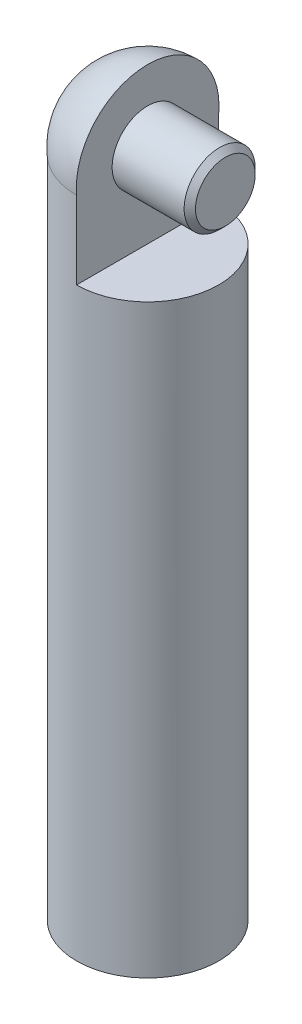
SolidWorks part; units mm, degrees
ref_plane "Front Plane" through (0, 0, 0) normal (0, 0, 1) x (1, 0, 0)
ref_plane "Top Plane" through (0, 0, 0) normal (0, 1, 0) x (1, 0, 0)
ref_plane "Right Plane" through (0, 0, 0) normal (1, 0, 0) x (0, 0, -1)
sketch "Sketch1" plane through (0, 0, 0) normal (0, 1, 0) x (1, 0, 0)
  circle A0 centre (0, 0) radius 19.05
  dimension "D1" = 38.1
extrude "Boss-Extrude1" add sketch "Sketch1" along normal blind 177.8
dome "Dome1" faces to dome 1 distance 20.828 reverse direction no elliptical dome no face at (0, 177.8, 19.05) parameters "D1"=20.828
sketch "Sketch2" plane through (0, 0, 0) normal (0, 0, 1) x (1, 0, 0)
  line L0 (19.05, 177.8) -> (-19.05, 177.8) construction
  line L1 (0, 198.628) -> (31.75, 198.628)
  line L2 (0, 198.628) -> (0, 156.972)
  line L3 (0, 156.972) -> (31.75, 156.972)
  line L4 (31.75, 198.628) -> (31.75, 156.972)
  line L5 (19.05, 0) -> (19.05, 177.8) construction
  point P6 (0, 177.8)
  dimension "D1" = 20.828
  dimension "D2" = 12.7
extrude "Cut-Extrude1" cut sketch "Sketch2" against normal through all both and the other way through all
sketch "Sketch3" plane through (0, 0, 0) normal (1, 0, 0) x (0, 0, -1)
  circle A0 centre (0, 179.5021) radius 9.525
  dimension "D1" = 19.05
extrude "Boss-Extrude2" add sketch "Sketch3" along normal blind 20.828
chamfer "Chamfer1" distance 1.524 angle 45 1 edges at (20.828, 189.0271, 0)
